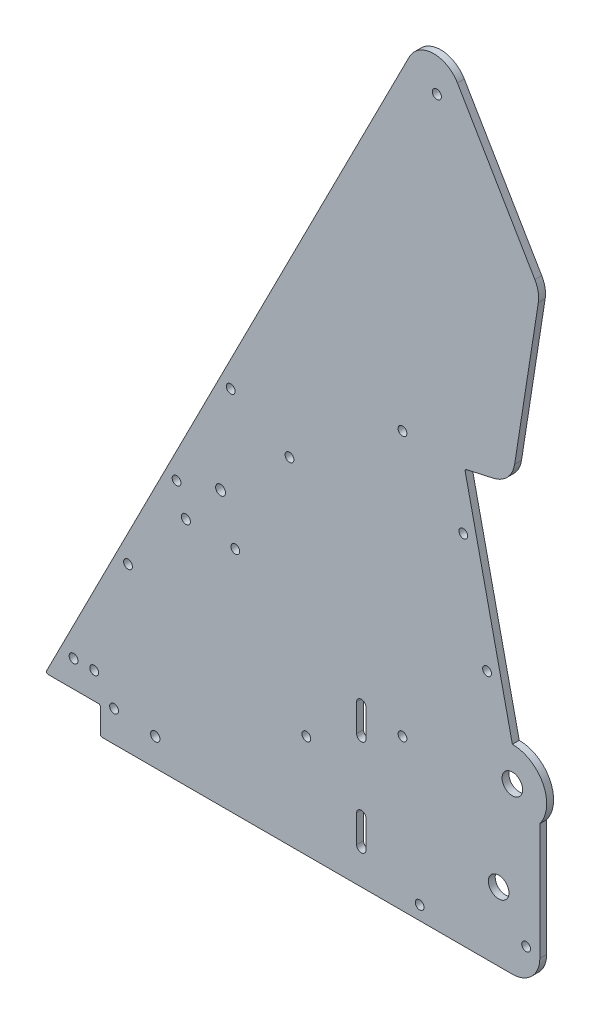
SolidWorks part; units mm, degrees
other "Markup1"
sketch "Sketch5"
ref_plane "Front Plane" through (0, 0, 0) normal (0, 0, 1) x (1, 0, 0)
ref_plane "Top Plane" through (0, 0, 0) normal (0, 1, 0) x (1, 0, 0)
ref_plane "Right Plane" through (0, 0, 0) normal (1, 0, 0) x (0, 0, -1)
sketch "Sketch1" plane through (0, 0, 0) normal (0, 0, 1) x (1, 0, 0)
  line L1 (228.6, -12.7) -> (228.6, 53.975)
  line L2 (178.7547, 351.4131) -> (0, 0)
  line L3 (228.6, 266.7) -> (178.7547, 351.4131)
  line L5 (0, 0) -> (25.4, 0)
  line L6 (25.4, 0) -> (25.4, -12.7)
  line L7 (25.4, -12.7) -> (228.6, -12.7)
  line L9 (215.9, 79.375) -> (193.9097, 178.5667)
  line L10 (193.9097, 178.5667) -> (215.6079, 183.377)
  line L11 (215.6079, 183.377) -> (228.6, 266.7)
  arc A0 (228.6, 53.975) -> (215.9, 79.375) centre (215.9, 63.5) ccw
  dimension "D7" = 12.7
  dimension "D8" = 76.2
  dimension "D10" = 31.75
  dimension "D2" = 279.4
  dimension "D3" = 25.4
  dimension "D4" = 215.9
  dimension "D5" = 394.2644
  dimension "D6" = 203.2
  dimension "D9" = 63.039
  dimension "D11" = 101.6
  dimension "D12" = 12.5
  dimension "D13" = 22.225
extrude "Boss-Extrude1" add sketch "Sketch1" along normal blind 3.175
sketch "Sketch2" plane through (0, 0, 3.175) normal (0, 0, 1) x (1, 0, 0)
  line L0 (178.7547, 351.4131) -> (0, 0) construction
  line L1 (25.4, -12.7) -> (228.6, -12.7) construction
  line L2 (215.9, 79.375) -> (193.9097, 178.5667) construction
  line L3 (193.9097, 178.5667) -> (215.6079, 183.377) construction
  line L4 (215.9, 79.375) -> (193.9097, 178.5667) construction
  line L10 (228.6, -12.7) -> (228.6, 53.975) construction
  circle A0 centre (64.9432, 94.0578) radius 2.0955
  circle A1 centre (180.975, 322.1643) radius 2.0955
  circle A2 centre (81.0071, 113.733) radius 2.286
  circle A3 centre (193.2078, 152.3944) radius 2.032
  circle A4 centre (215.9, 63.5) radius 4.7625
  circle A7 centre (173.0375, -6.35) radius 2.032
  circle A8 centre (204.203, 102.7985) radius 2.032
  circle A26 centre (209.55, 19.05) radius 4.7625
  circle A28 centre (60.6578, 107.342) radius 2.032
  arc A30 (228.6, 53.975) -> (215.9, 79.375) centre (215.9, 63.5) ccw construction
  circle A31 centre (165.1, 179.3875) radius 2.032
  circle A32 centre (87.825, 93.5227) radius 2.032
  circle A33 centre (112.8724, 142.7633) radius 2.032
  circle A34 centre (85.7052, 156.5826) radius 2.032
  dimension "D3" = 4.191
  dimension "D5" = 4.191
  dimension "D9" = 4.572
  dimension "D20" = 9.525
  dimension "D23" = 9.525
  dimension "D18" = 4.064
  dimension "D26" = 4.064
  dimension "D14" = 4.064
  dimension "D10" = 4.064
  dimension "D2" = 15.24
  dimension "D6" = 15.24
  dimension "D7" = 25.4
  dimension "D8" = 20.6375
  dimension "D21" = 44.45
  dimension "D22" = 6.35
  dimension "D19" = 160.3375
  dimension "D24" = 44.45
  dimension "D25" = 6.35
  dimension "D27" = 25.4
  dimension "D28" = 50.8
  dimension "D29" = 6.35
  dimension "D17" = 6.35
  dimension "D33" = 55.5625
  dimension "D15" = 114.3
  dimension "D4" = 180.975
extrude "Cut-Extrude1" cut sketch "Sketch2" against normal through all
sketch "Sketch7" plane through (0, 0, 3.175) normal (0, 0, 1) x (1, 0, 0)
  line L0 (146.05, 3.175) -> (146.05, 15.875) construction
  line L1 (143.891, 3.175) -> (143.891, 15.875)
  line L2 (148.209, 3.175) -> (148.209, 15.875)
  line L3 (146.05, 47.625) -> (146.05, 60.325) construction
  line L4 (143.891, 47.625) -> (143.891, 60.325)
  line L5 (148.209, 47.625) -> (148.209, 60.325)
  line L6 (25.4, -12.7) -> (228.6, -12.7) construction
  line L12 (228.6, -12.7) -> (228.6, 53.975) construction
  line L13 (25.4, -12.7) -> (228.6, -12.7) construction
  arc A0 (143.891, 3.175) -> (148.209, 3.175) centre (146.05, 3.175) ccw
  arc A1 (148.209, 15.875) -> (143.891, 15.875) centre (146.05, 15.875) ccw
  arc A2 (143.891, 47.625) -> (148.209, 47.625) centre (146.05, 47.625) ccw
  arc A3 (148.209, 60.325) -> (143.891, 60.325) centre (146.05, 60.325) ccw
  circle A8 centre (50.8, 0) radius 2.159
  point P2 (146.05, 9.525)
  point P9 (146.05, 53.975)
  dimension "D1" = 4.318
  dimension "D5" = 4.318
  dimension "D2" = 12.7
  dimension "D3" = 12.7
  dimension "D4" = 44.45
  dimension "D6" = 95.25
  dimension "D7" = 82.55
  dimension "D8" = 15.875
  dimension "D9" = 12.7
extrude "Cut-Extrude2" cut sketch "Sketch7" against normal through all
sketch "Sketch10" plane through (0, 0, 3.175) normal (0, 0, 1) x (1, 0, 0)
  circle A0 centre (120.65, 34.925) radius 2.032
  circle A1 centre (165.1, 57.15) radius 2.032
  circle A2 centre (13.0465, 12.3347) radius 2.032
  circle A3 centre (22.5715, 12.3347) radius 2.032
  circle A4 centre (38.2114, 62.6398) radius 2.032
  dimension "D1" = 4.064
  dimension "D3" = 34.925
  dimension "D2" = 120.65
  dimension "D4" = 63.5
  dimension "D5" = 69.85
extrude "Cut-Extrude3" cut sketch "Sketch10" against normal up to next
fillet "Fillet1" radius 12.7 4 edges at (228.6, -12.7, 1.5875) (178.7547, 351.4131, 1.5875) (215.6079, 183.377, 1.5875) (228.6, 266.7, 1.5875)
fillet "Fillet2" radius 0.7937 4 edges at (25.4, -12.7, 1.5875) (25.4, 0, 1.5875) (193.9097, 178.5667, 1.5875) (0, 0, 1.5875)
sketch "Sketch12" plane through (0, 0, 3.175) normal (0, 0, 1) x (1, 0, 0)
  circle A0 centre (31.75, 1.5875) radius 2.032
  circle A1 centre (173.0375, -6.35) radius 2.032
  circle A2 centre (222.25, 1.5875) radius 2.032
  dimension "D1" = 4.064
extrude "Cut-Extrude5" cut sketch "Sketch12" against normal through all
equation "\"D6@Sketch2\"=\"D2@Sketch2\""
